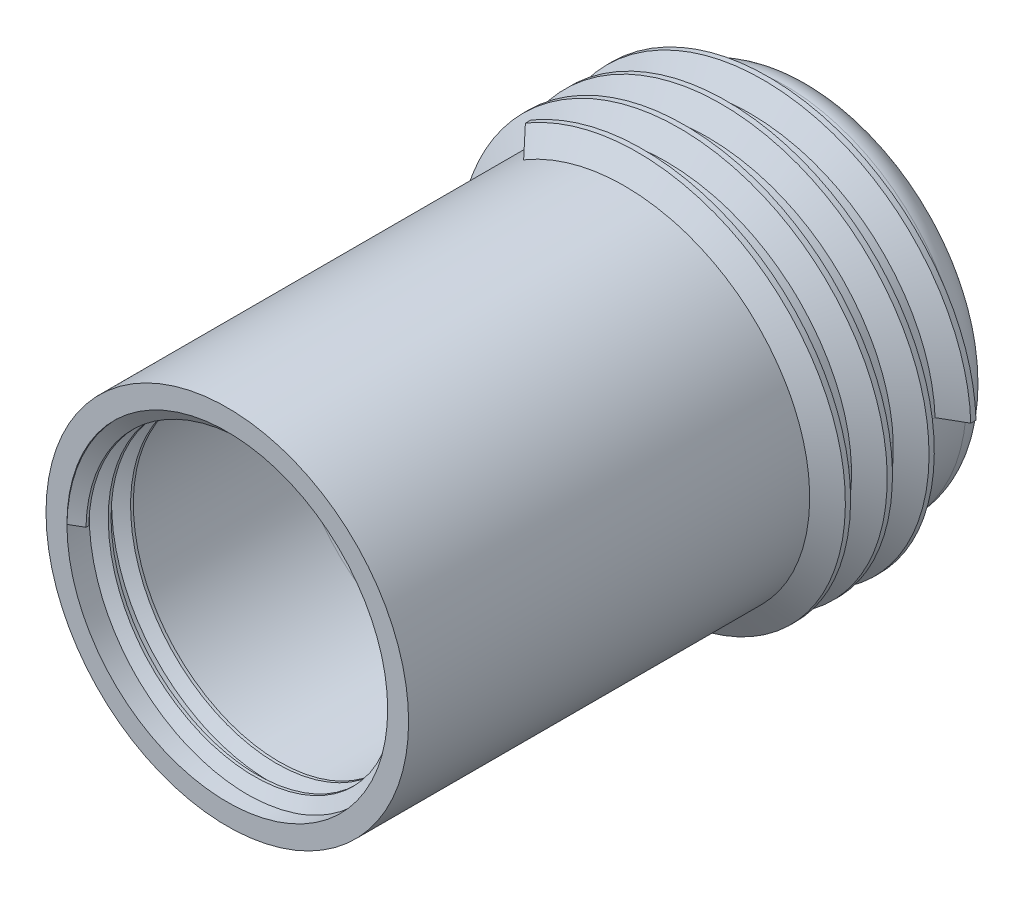
SolidWorks part; units mm, degrees
ref_plane "Plan de face" through (0, 0, 0) normal (0, 0, 1) x (1, 0, 0)
ref_plane "Plan de dessus" through (0, 0, 0) normal (0, 1, 0) x (1, 0, 0)
ref_plane "Plan de droite" through (0, 0, 0) normal (1, 0, 0) x (0, 0, -1)
sketch "Sketch1" plane through (0, 0, 0) normal (0, 0, 1) x (1, 0, 0)
  circle A0 centre (0, 0) radius 5.5
  circle A1 centre (0, 0) radius 6.5
  dimension "D1" = 11
  dimension "D2" = 1
extrude "Boss-Extrude1" add sketch "Sketch1" along normal blind 20
sketch "Sketch2" plane through (0, 0, 0) normal (0, 0, -1) x (-1, 0, 0)
  circle A1 centre (0, 0) radius 6.5
  circle A2 centre (0, 0) radius 6.5
  dimension "D1" = 0
extrude "Boss-Extrude2" add sketch "Sketch2" along normal blind 1
sketch "Sketch10" plane through (0, 0, 20) normal (0, 0, 1) x (1, 0, 0)
  circle A0 centre (0, 0) radius 5.75
  circle A1 centre (0, 0) radius 5.5 construction
  dimension "D1" = 0.25
extrude "Cut-Extrude2" cut sketch "Sketch10" against normal blind 9
fillet "Fillet2" radius 2 1 edges at (5.75, 0, 11)
thread "Thread3" pitch 1.5 method extrude profile "Thread Profile4" start angle 0, offset 1, length 5, pitch 1.5, diameter 13
ref_plane "Plane4" through (6.5, 0, 0) normal (0, -1, 0) x (1, 0, 0)
sketch "Thread Profile4" plane through (6.5, 0, 0) normal (0, -1, 0) x (1, 0, 0)
  line L0 (0, 0) -> (0, 1.5) construction
  line L1 (0, 0) -> (0.8119, 0.4687)
  line L2 (0.8119, 0.4687) -> (0.8119, 0.6562)
  line L3 (0.8119, 0.6562) -> (0, 1.125)
  line L4 (0.8119, 0.5625) -> (0, 0.5625) construction
  line L11 (0, 0) -> (0, 1.125)
  point P2 (0, 0)
  dimension "Pitch" = 1.5
  dimension "Profile_Angle" = 60
  dimension "Profile_Land" = 0.1875
  dimension "Profile_Height" = 0.8119
sketch "Sketch9" plane through (0, 0, -1) normal (0, 0, -1) x (-1, 0, 0)
  circle A0 centre (0, 0) radius 4.5
  dimension "D1" = 9
extrude "Cut-Extrude1" cut sketch "Sketch9" against normal blind 10
chamfer "Chamfer1" distance 1 angle 45 1 edges at (-4.5, 0, 0)
fillet "Fillet1" radius 1 1 edges at (-6.5, 0, -1)
thread "Thread4" pitch 0.8 method extrude profile "Thread Profile6" start angle 0, offset 0, length 2, pitch 0.8, diameter 11.5
ref_plane "Plane6" through (-5.75, 0, 20) normal (0, 1, 0) x (1, 0, 0)
sketch "Thread Profile6" plane through (-5.75, 0, 20) normal (0, 1, 0) x (1, 0, 0)
  line L0 (0, 0) -> (0, 0.8) construction
  line L1 (0, 0) -> (0.433, 0.25)
  line L2 (0.433, 0.25) -> (0.433, 0.35)
  line L3 (0.433, 0.35) -> (0, 0.6)
  line L4 (0.433, 0.3) -> (0, 0.3) construction
  line L11 (0, 0) -> (0, 0.6)
  point P2 (0, 0)
  dimension "Pitch" = 0.8
  dimension "Profile_Angle" = 60
  dimension "Profile_Land" = 0.1
  dimension "Profile_Height" = 0.433
